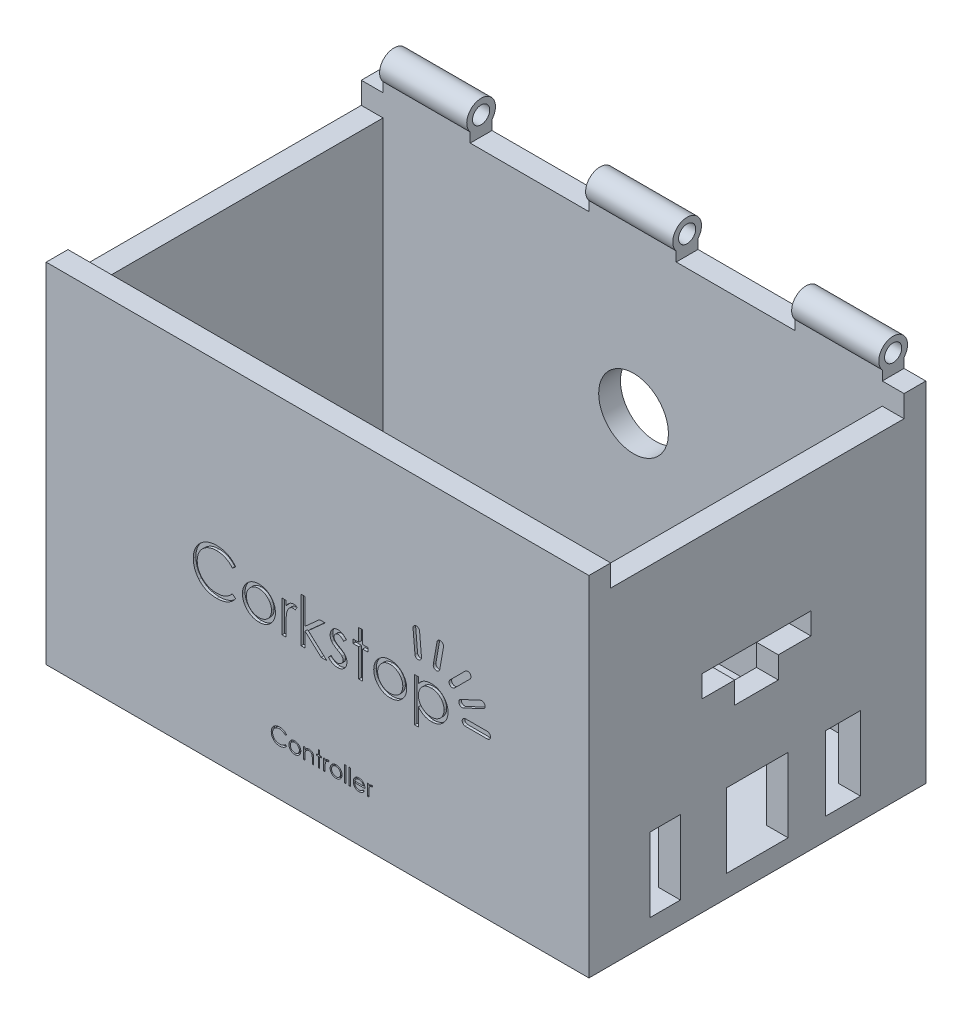
SolidWorks part; units mm, degrees
ref_plane "Front Plane" through (0, 0, 0) normal (0, 0, 1) x (1, 0, 0)
ref_plane "Top Plane" through (0, 0, 0) normal (0, 1, 0) x (1, 0, 0)
ref_plane "Right Plane" through (0, 0, 0) normal (1, 0, 0) x (0, 0, -1)
sketch "Sketch1" plane through (0, 0, 0) normal (0, 1, 0) x (1, 0, 0)
  line L1 (-79.1, 49.1) -> (79.1, 49.1)
  line L2 (-79.1, 49.1) -> (-79.1, -49.1)
  line L3 (-79.1, -49.1) -> (79.1, -49.1)
  line L4 (79.1, 49.1) -> (79.1, -49.1)
  line L5 (-79.1, 49.1) -> (79.1, -49.1) construction
  line L6 (-79.1, -49.1) -> (79.1, 49.1) construction
  point P0 (0, 0)
  dimension "D1" = 158.2
  dimension "D2" = 98.2
extrude "Boss-Extrude1" add sketch "Sketch1" along normal blind 6.35
sketch "Sketch2" plane through (0, 0, 49.1) normal (0, 0, 1) x (1, 0, 0)
  line L1 (-79.1, 101.6) -> (79.1, 101.6)
  line L2 (-79.1, 101.6) -> (-79.1, 6.35)
  line L3 (-79.1, 6.35) -> (79.1, 6.35)
  line L4 (79.1, 101.6) -> (79.1, 6.35)
  line L5 (-79.1, 101.6) -> (79.1, 6.35) construction
  line L6 (-79.1, 6.35) -> (79.1, 101.6) construction
  point P0 (0, 53.975)
  dimension "D1" = 95.25
extrude "Boss-Extrude2" add sketch "Sketch2" against normal blind 6.35
sketch "Sketch3" plane through (-79.1, 0, 0) normal (-1, 0, 0) x (0, 0, 1)
  line L1 (-42.75, 101.6) -> (42.75, 101.6)
  line L2 (-42.75, 101.6) -> (-42.75, 6.35)
  line L3 (-42.75, 6.35) -> (42.75, 6.35)
  line L4 (42.75, 101.6) -> (42.75, 6.35)
  line L5 (-42.75, 101.6) -> (42.75, 6.35) construction
  line L6 (-42.75, 6.35) -> (42.75, 101.6) construction
  point P0 (0, 53.975)
  dimension "D1" = 95.25
extrude "Boss-Extrude3" add sketch "Sketch3" against normal blind 6.35
sketch "Sketch4" plane through (0, 0, -49.1) normal (0, 0, -1) x (-1, 0, 0)
  line L1 (-79.1, 101.6) -> (79.1, 101.6)
  line L2 (-79.1, 101.6) -> (-79.1, 6.35)
  line L3 (-79.1, 6.35) -> (79.1, 6.35)
  line L4 (79.1, 101.6) -> (79.1, 6.35)
  line L5 (-79.1, 101.6) -> (79.1, 6.35) construction
  line L6 (-79.1, 6.35) -> (79.1, 101.6) construction
  point P0 (0, 53.975)
  dimension "D1" = 95.25
extrude "Boss-Extrude4" add sketch "Sketch4" against normal blind 6.35
sketch "Sketch5" plane through (79.1, 0, 0) normal (1, 0, 0) x (0, 0, -1)
  line L0 (42.75, 101.6) -> (42.75, 6.35) construction
  line L1 (-42.75, 27.94) -> (42.75, 27.94)
  line L2 (-42.75, 27.94) -> (-42.75, 101.6)
  line L3 (-42.75, 101.6) -> (42.75, 101.6)
  line L4 (42.75, 27.94) -> (42.75, 101.6)
  line L5 (-42.75, 27.94) -> (42.75, 101.6) construction
  line L6 (-42.75, 101.6) -> (42.75, 27.94) construction
  line L7 (42.75, 101.6) -> (42.75, 6.35) construction
  line L8 (42.75, 101.6) -> (49.1, 101.6) construction
  point P0 (0, 64.77)
  dimension "D1" = 73.66
  dimension "D2" = 0
extrude "Boss-Extrude5" add sketch "Sketch5" against normal blind 6.35
sketch "Sketch6" plane through (79.1, 0, 0) normal (1, 0, 0) x (0, 0, -1)
  line L0 (-42.75, 27.94) -> (42.75, 27.94) construction
  line L1 (-22.43, 27.94) -> (-8.968, 27.94)
  line L2 (-22.43, 27.94) -> (-22.43, 6.35)
  line L3 (-22.43, 6.35) -> (-8.968, 6.35)
  line L4 (-8.968, 27.94) -> (-8.968, 6.35)
  line L5 (-42.75, 6.35) -> (42.75, 6.35) construction
  line L6 (42.75, 6.35) -> (-42.75, 6.35) construction
  line L7 (8.968, 27.94) -> (19.89, 27.94)
  line L8 (8.968, 27.94) -> (8.968, 6.35)
  line L9 (8.968, 6.35) -> (19.89, 6.35)
  line L10 (19.89, 27.94) -> (19.89, 6.35)
  line L11 (-42.75, 6.35) -> (-42.75, 27.94) construction
  line L12 (42.75, 27.94) -> (42.75, 6.35) construction
  line L14 (-42.75, 27.94) -> (-31.32, 27.94)
  line L15 (-42.75, 27.94) -> (-42.75, 6.35)
  line L16 (-42.75, 6.35) -> (-31.32, 6.35)
  line L17 (-31.32, 27.94) -> (-31.32, 6.35)
  line L18 (42.75, 27.94) -> (30.05, 27.94)
  line L19 (42.75, 27.94) -> (42.75, 6.35)
  line L20 (42.75, 6.35) -> (30.05, 6.35)
  line L21 (30.05, 27.94) -> (30.05, 6.35)
  dimension "D1" = 13.462
  dimension "D2" = 10.922
  dimension "D3" = 20.32
  dimension "D4" = 22.86
  dimension "D5" = 0
  dimension "D6" = 11.43
  dimension "D7" = 12.7
  dimension "D8" = 17.936
extrude "Boss-Extrude6" add sketch "Sketch6" against normal blind 6.35
sketch "Çizim2" plane through (79.1, 0, 0) normal (1, 0, 0) x (0, 0, -1)
  line L0 (-49.1, 0) -> (49.1, 0) construction
  line L1 (-16.125, 60.325) -> (15.625, 60.325)
  line L2 (-16.125, 60.325) -> (-16.125, 53.975)
  line L3 (-16.125, 53.975) -> (-6.6, 53.975)
  line L4 (15.625, 60.325) -> (15.625, 53.975)
  line L5 (-16.125, 60.325) -> (15.625, 53.975) construction
  line L6 (-16.125, 53.975) -> (15.625, 60.325) construction
  line L7 (-42.75, 101.6) -> (-42.75, 6.35) construction
  line L8 (6.1, 53.975) -> (15.625, 53.975)
  line L9 (-6.6, 47.625) -> (6.1, 47.625)
  line L10 (-6.6, 47.625) -> (-6.6, 53.975)
  line L12 (6.1, 47.625) -> (6.1, 53.975)
  line L13 (-6.6, 47.625) -> (-0.25, 50.8) construction
  line L14 (-6.6, 53.975) -> (6.1, 47.625) construction
  point P0 (-0.25, 57.15)
  point P9 (-0.25, 50.8)
  dimension "D1" = 60.325
  dimension "D2" = 53.975
  dimension "D3" = 31.75
  dimension "D4" = 42.5
  dimension "D5" = 12.7
  dimension "D6" = 42.5
  dimension "D7" = 6.35
extrude "Kes-Ekstrüzyon1" cut sketch "Çizim2" against normal blind 6.35
sketch "Çizim3" plane through (0, 0, -49.1) normal (0, 0, -1) x (-1, 0, 0)
  line L0 (-79.1, 0) -> (79.1, 0) construction
  line L1 (-79.1, 101.6) -> (-79.1, 0) construction
  circle A0 centre (-0.25, 57.15) radius 10.16
  dimension "D1" = 20.32
  dimension "D2" = 57.15
  dimension "D3" = 78.85
extrude "Kes-Ekstrüzyon2" cut sketch "Çizim3" against normal blind 6.35
sketch "Çizim4" plane through (-79.1, 0, 0) normal (-1, 0, 0) x (0, 0, 1)
  line L0 (-49.1, 0) -> (49.1, 0) construction
  circle A0 centre (0, 41.275) radius 4.826
  dimension "D1" = 41.275
extrude "Kes-Ekstrüzyon3" cut sketch "Çizim4" against normal blind 6.35
sketch "Çizim5" plane through (79.1, 0, 0) normal (1, 0, 0) x (0, 0, -1)
  line L0 (42.75, 6.35) -> (42.75, 101.6) construction
  line L1 (-42.75, 101.6) -> (42.75, 101.6)
  line L2 (-42.75, 101.6) -> (-42.75, 95.25)
  line L3 (-42.75, 95.25) -> (42.75, 95.25)
  line L4 (42.75, 101.6) -> (42.75, 95.25)
  dimension "D1" = 6.35
extrude "Kes-Ekstrüzyon4" cut sketch "Çizim5" against normal blind 6.35
sketch "Çizim6" plane through (-79.1, 0, 0) normal (-1, 0, 0) x (0, 0, 1)
  line L1 (-42.75, 101.6) -> (42.75, 101.6)
  line L2 (-42.75, 101.6) -> (-42.75, 95.25)
  line L3 (-42.75, 95.25) -> (42.75, 95.25)
  line L4 (42.75, 101.6) -> (42.75, 95.25)
extrude "Kes-Ekstrüzyon5" cut sketch "Çizim6" against normal blind 6.35
sketch "Çizim7" plane through (0, 0, 49.1) normal (0, 0, 1) x (1, 0, 0)
  line L0 (-72.75, 6.35) -> (-72.75, 95.25) construction
  line L1 (-72.75, 6.35) -> (72.75, 6.35) construction
  text T0 "Corkstop" font "Century Gothic" height 12.7
  dimension "D1" = 35.56
  dimension "D2" = 35.56
extrude "Kes-Ekstrüzyon6" cut sketch "Çizim7" against normal blind 0.762
sketch "Çizim12" plane through (0, 0, 49.1) normal (0, 0, 1) x (1, 0, 0)
  line L2 (27.8371, 62.676) -> (28.3905, 56.3502)
  line L4 (29.7431, 62.8428) -> (30.2966, 56.517)
  arc A1 (28.3905, 56.3502) -> (30.2966, 56.517) centre (29.3435, 56.4336) ccw
  arc A2 (29.7431, 62.8428) -> (27.8371, 62.676) centre (28.7901, 62.7594) ccw
  dimension "D1" = 3.81
  dimension "D2" = 6.35
  dimension "D3" = 1.9133
  dimension "D4" = 6.35
  dimension "D5" = 6.35
extrude "Kes-Ekstrüzyon7" cut sketch "Çizim12" against normal blind 0.762
sketch "Çizim14" plane through (0, 0, 49.1) normal (0, 0, 1) x (1, 0, 0)
  line L1 (43.1131, 47.4484) -> (49.4631, 47.4484)
  line L3 (43.0101, 45.5351) -> (49.4631, 45.5351)
  arc A0 (49.4631, 45.5351) -> (49.4631, 47.4484) centre (49.4631, 46.4917) ccw
  arc A1 (43.1131, 47.4484) -> (43.0101, 45.5351) centre (43.1131, 46.489) ccw
  dimension "D1" = 1.9133
  dimension "D2" = 6.35
  dimension "D3" = 5.08
extrude "Kes-Ekstrüzyon8" cut sketch "Çizim14" against normal blind 0.762
sketch "Çizim15" plane through (0, 0, 49.1) normal (0, 0, 1) x (1, 0, 0)
  line L0 (41.7144, 51.6199) -> (47.4695, 54.3035)
  line L1 (42.4297, 49.8424) -> (48.2781, 52.5695)
  line L2 (49.4631, 47.4484) -> (43.1131, 47.4484) construction
  arc A0 (48.2781, 52.5695) -> (47.4695, 54.3035) centre (47.8738, 53.4365) ccw
  arc A1 (41.7144, 51.6199) -> (42.4297, 49.8424) centre (42.1199, 50.7504) ccw
  dimension "D1" = 1.9133
  dimension "D2" = 6.35
  dimension "D3" = 5.842
  dimension "D4" = 3.302
extrude "Kes-Ekstrüzyon9" cut sketch "Çizim15" against normal blind 0.762
sketch "Çizim18" plane through (0, 0, 49.1) normal (0, 0, 1) x (1, 0, 0)
  line L0 (38.6008, 54.9998) -> (43.0909, 59.4899)
  line L1 (39.8809, 53.5741) -> (44.4438, 58.137)
  arc A0 (44.4438, 58.137) -> (43.0909, 59.4899) centre (43.7674, 58.8135) ccw
  arc A1 (38.6008, 54.9998) -> (39.8809, 53.5741) centre (39.2792, 54.3214) ccw
  dimension "D1" = 1.9133
  dimension "D2" = 6.35
sketch "Çizim19" plane through (0, 0, 49.1) normal (0, 0, 1) x (1, 0, 0)
  line L0 (33.7349, 56.4717) -> (34.8376, 62.7252)
  line L1 (35.6013, 56.0381) -> (36.7218, 62.393)
  arc A0 (36.7218, 62.393) -> (34.8376, 62.7252) centre (35.7797, 62.5591) ccw
  arc A1 (33.7349, 56.4717) -> (35.6013, 56.0381) centre (34.6798, 56.3051) ccw
  dimension "D1" = 1.9133
  dimension "D2" = 6.35
extrude "Kes-Ekstrüzyon12" cut sketch "Çizim19" against normal blind 0.762
extrude "Kes-Ekstrüzyon13" cut sketch "Çizim18" against normal blind 0.762
sketch "Çizim27" plane through (0, 0, 49.1) normal (0, 0, 1) x (1, 0, 0)
  text T0 "Controller\r\n" font "Century Gothic" height 4.572
sketch "Çizim21" plane through (-72.75, 0, 0) normal (1, 0, 0) x (0, 0, -1)
  line L1 (42.75, 101.6) -> (49.1, 101.6)
  line L2 (42.75, 101.6) -> (42.75, 104.3997)
  line L4 (49.1, 101.6) -> (49.1, 104.3997)
  arc A0 (49.1, 104.3997) -> (42.75, 104.3997) centre (45.925, 107.1365) ccw
  dimension "D1" = 6.35
  dimension "D2" = 3.175
extrude "Yükseklik-Ekstrüzyon2" add sketch "Çizim21" along normal blind 25.4
sketch "Çizim22" plane through (72.75, 0, 0) normal (-1, 0, 0) x (0, 0, 1)
  line L0 (-49.1, 101.6) -> (-42.75, 101.6)
  line L1 (-49.1, 101.6) -> (-49.1, 104.3995)
  line L2 (-42.75, 101.6) -> (-42.75, 104.3995)
  arc A0 (-42.75, 104.3995) -> (-49.1, 104.3995) centre (-45.925, 107.1364) ccw
  dimension "D1" = 6.35
  dimension "D2" = 3.175
extrude "Yükseklik-Ekstrüzyon3" add sketch "Çizim22" along normal blind 25.4
ref_plane "Düzlem2" through (12.7, 0, 0) normal (-1, 0, 0) x (0, 0, 1)
sketch "Çizim23" plane through (12.7, 0, 0) normal (-1, 0, 0) x (0, 0, 1)
  line L0 (-49.1, 101.6) -> (-42.75, 101.6)
  line L1 (-49.1, 101.6) -> (-49.1, 104.3997)
  line L2 (-42.75, 101.6) -> (-42.75, 104.3997)
  arc A0 (-42.75, 104.3997) -> (-49.1, 104.3997) centre (-45.925, 107.1365) ccw
  dimension "D1" = 6.35
  dimension "D2" = 3.175
extrude "Yükseklik-Ekstrüzyon4" add sketch "Çizim23" along normal blind 25.4
extrude "Yükseklik-Ekstrüzyon5" add sketch "Çizim23<2>" along normal blind 12.7
sketch "Çizim23<2>" plane through (12.7, 0, 0) normal (-1, 0, 0) x (0, 0, 1) same geometry as "Çizim23"
sketch "Çizim24" plane through (12.7, 0, 0) normal (-1, 0, 0) x (0, 0, 1)
  circle A0 centre (-45.925, 107.1365) radius 2.5
extrude "Kes-Ekstrüzyon14" cut sketch "Çizim24" along normal blind 25.4 contours A0
sketch "Çizim25" plane through (72.75, 0, 0) normal (1, 0, 0) x (0, 0, -1)
  circle A0 centre (45.925, 107.1364) radius 2.5
extrude "Kes-Ekstrüzyon15" cut sketch "Çizim25" against normal blind 25.4
sketch "Çizim26" plane through (-72.75, 0, 0) normal (-1, 0, 0) x (0, 0, 1)
  circle A0 centre (-45.925, 107.1365) radius 2.5
extrude "Kes-Ekstrüzyon16" cut sketch "Çizim26" against normal blind 25.4
extrude "Kes-Ekstrüzyon17" cut sketch "Çizim27" against normal blind 0.762
